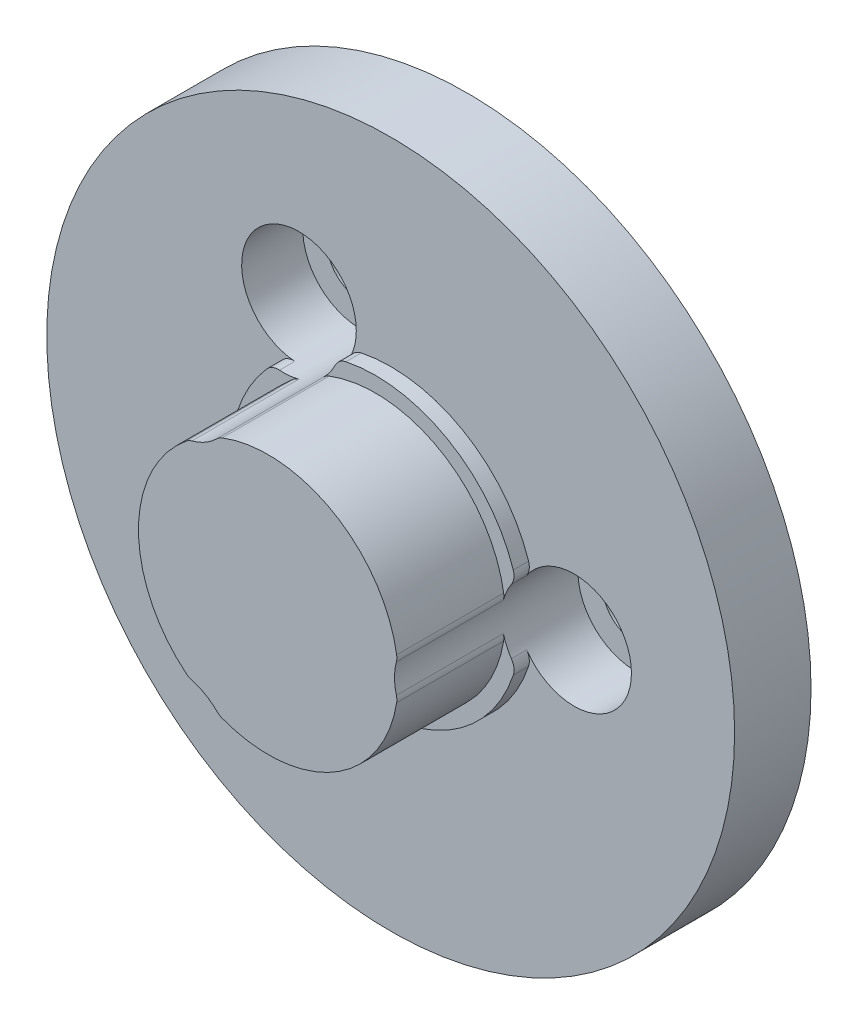
SolidWorks part; units mm, degrees
material "ABS"
ref_plane "Front Plane" through (0, 0, 0) normal (0, 0, 1) x (1, 0, 0)
ref_plane "Top Plane" through (0, 0, 0) normal (0, 1, 0) x (1, 0, 0)
ref_plane "Right Plane" through (0, 0, 0) normal (1, 0, 0) x (0, 0, -1)
sketch "Sketch1" plane through (0, 0, 31) normal (0, 0, 1) x (1, 0, 0)
  circle A0 centre (0, 0) radius 22.5
  circle A1 centre (-6, 10.3923) radius 2.15
  circle A2 centre (-6, -10.3923) radius 2.15
  circle A3 centre (12, 0) radius 2.15
  dimension "D1" = 45
  dimension "D2" = 4.3
  dimension "D3" = 4.3
  dimension "D4" = 4.3
extrude "Boss-Extrude1" add sketch "Sketch1" along normal blind 5
sketch "Sketch2" plane through (0, 0, 36) normal (0, 0, 1) x (1, 0, 0)
  circle A0 centre (-6, 10.3923) radius 3.75
  circle A1 centre (12, 0) radius 3.75
  circle A2 centre (-6, -10.3923) radius 3.75
  dimension "D1" = 7.5
  dimension "D2" = 7.5
  dimension "D3" = 7.5
extrude "Cut-Extrude1" cut sketch "Sketch2" against normal blind 4
sketch "Sketch3" plane through (0, 0, 36) normal (0, 0, 1) x (1, 0, 0)
  circle A0 centre (0, 0) radius 9.5
  circle M2 centre (-6, 10.3923) radius 3.75
  circle M3 centre (12, 0) radius 3.75
  circle M4 centre (-6, -10.3923) radius 3.75
  dimension "D1" = 19
extrude "Boss-Extrude2" add sketch "Sketch3" along normal blind 1 contours A0 M3 M2 M4 region at (0, 0, 36)
sketch "Sketch4" plane through (0, 0, 37) normal (0, 0, 1) x (1, 0, 0)
  circle A0 centre (0, 0) radius 8.5
  arc M2 (9.1745, -2.4655) -> (9.1745, 2.4655) centre (12, 0) cw
  arc M4 (-2.452, 9.1781) -> (-6.7225, 6.7126) centre (-6, 10.3923) cw
  arc M6 (-6.7225, -6.7126) -> (-2.452, -9.1781) centre (-6, -10.3923) cw
  dimension "D1" = 17
extrude "Boss-Extrude3" add sketch "Sketch4" along normal blind 7 contours A0 M2 M4 M6 region at (0, 0, 37)
fillet "Fillet1" radius 1 12 edges at (9.1745, 2.4655, 36.5) (-6.7225, 6.7126, 36.5) (-2.452, -9.1781, 36.5) (-2.452, 9.1781, 36.5) (-6.7225, -6.7126, 36.5) (9.1745, -2.4655, 36.5) (8.4245, 1.1306, 40.5) (-5.1913, 6.7305, 40.5) (-3.2332, -7.8611, 40.5) (-3.2332, 7.8611, 40.5) (-5.1913, -6.7305, 40.5) (8.4245, -1.1306, 40.5)
equation "\"thighLength\"=185"
equation "\"legLength\"=200"
equation "\"m3Thru\"=3.2"
equation "\"m4Thru\"=4.3"
equation "\"m3Insert\"=4.2"
equation "\"m4Insert\"=5.3"
equation "\"shoulder5mm\"=5.1"
equation "\"6706out\"=37.125"
equation "\"6706in\"=30"
equation "\"6904out\"=30.125"
equation "\"6904in\"=17"
equation "\"D2@Sketch1\"=\"m4Thru\""
equation "\"D3@Sketch1\"=\"m4Thru\""
equation "\"D4@Sketch1\"=\"m4Thru\""
